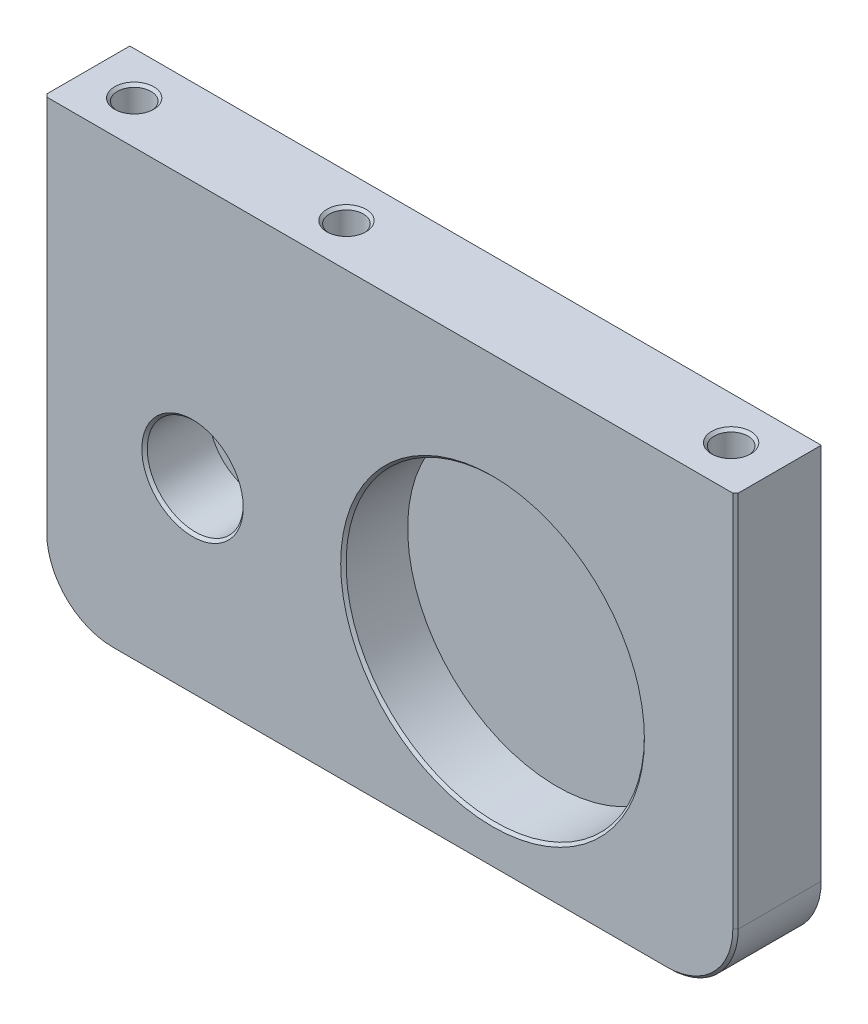
SolidWorks part; units mm, degrees
ref_plane "Front Plane" through (0, 0, 0) normal (0, 0, 1) x (1, 0, 0)
ref_plane "Top Plane" through (0, 0, 0) normal (0, 1, 0) x (1, 0, 0)
ref_plane "Right Plane" through (0, 0, 0) normal (1, 0, 0) x (0, 0, -1)
sketch "Sketch1" plane through (0, 0, 4937.9482) normal (0, 0, 1) x (1, 0, 0)
  line L10 (-33.225, 19.05) -> (18, 19.05)
  line L11 (-33.225, 19.05) -> (-33.225, -14)
  line L12 (-33.225, -14) -> (18, -14)
  line L13 (18, 19.05) -> (18, -14)
  circle A2 centre (0, 0) radius 11.05 construction
  circle A3 centre (-22.225, 0) radius 3.556 construction
  point P4 (-22.225, 0)
  dimension "D2" = 7.112
  dimension "D5" = 19.05
  dimension "D6" = 11
  dimension "D3" = 22.225
  dimension "D1" = 22.1
  dimension "D8" = 51.225
  dimension "D4" = 14
  dimension "D7" = 18
extrude "Boss-Extrude1" add sketch "Sketch1" against normal blind 6.35
sketch "Sketch8" plane through (0, 19.05, 0) normal (0, 1, 0) x (1, 0, 0)
  line L0 (-33.225, -4934.7732) -> (18, -4934.7732) construction
  line L1 (-33.225, -4931.5982) -> (-33.225, -4937.9482) construction
  line L2 (18, -4931.5982) -> (18, -4937.9482) construction
  circle A1 centre (-29.725, -4934.7732) radius 1.25
  circle A2 centre (-14, -4934.7732) radius 1.25
  circle A3 centre (14.5, -4934.7732) radius 1.25
  dimension "D1" = 2.5
  dimension "D2" = 3.5
  dimension "D3" = 3.5
  dimension "D4" = 14
extrude "Cut-Extrude4" cut sketch "Sketch8" against normal blind 15
fillet "Fillet3" radius 5.08 2 edges at (18, -14, 4934.7732) (-33.225, -14, 4934.7732)
sketch "Sketch10" plane through (0, 0, 4937.9482) normal (0, 0, 1) x (1, 0, 0)
  circle A0 centre (-22.225, 0) radius 3.556 construction
  circle A1 centre (0, 0) radius 11.05 construction
  circle A2 centre (-22.225, 0) radius 3.556
  circle A3 centre (0, 0) radius 11.05
extrude "Cut-Extrude5" cut sketch "Sketch10" against normal offset from surface (4.7625 mm away) 1.5875 up to face at (-7.6125, -1.6407, 4931.5982)
chamfer "Chamfer2" distance 0.2 angle 45 10 edges at (18, 5.065, 4937.9482) (-33.225, 5.065, 4937.9482) (-31.7371, -12.5121, 4937.9482) (16.5121, -12.5121, 4937.9482) (-7.6125, -14, 4937.9482) (14.5, 19.05, 4936.0232) (-14, 19.05, 4936.0232) (-29.725, 19.05, 4936.0232) (-18.669, 0, 4937.9482) (11.05, 0, 4937.9482)
